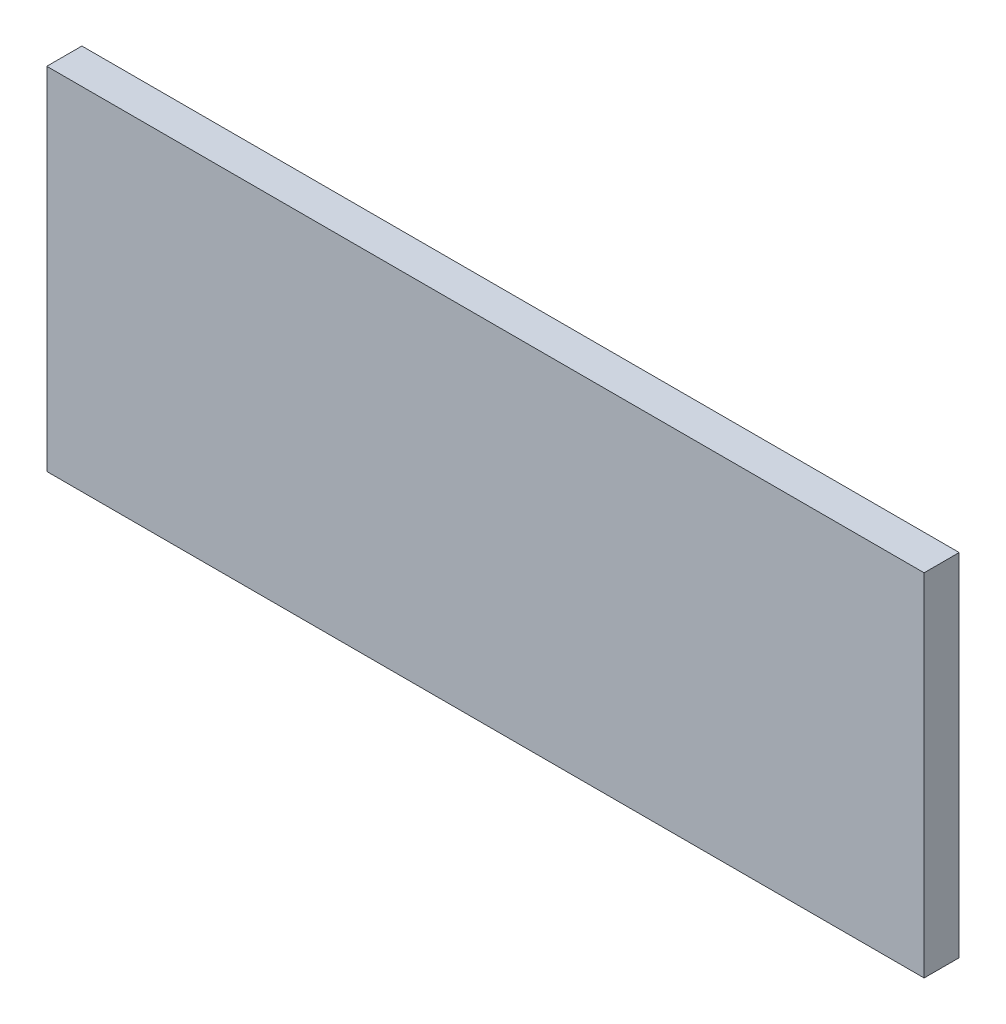
SolidWorks part; units mm, degrees
material "Лист 6,0 ГОСТ 19903-2015 / Ст3сп ГОСТ 14637-89"
ref_plane "Спереди" through (0, 0, 0) normal (0, 0, 1) x (1, 0, 0)
ref_plane "Сверху" through (0, 0, 0) normal (0, 1, 0) x (1, 0, 0)
ref_plane "Справа" through (0, 0, 0) normal (1, 0, 0) x (0, 0, -1)
sketch "Эскиз1" plane through (0, 0, 0) normal (0, 0, 1) x (1, 0, 0)
  line L1 (-75, -30) -> (75, -30)
  line L2 (-75, -30) -> (-75, 30)
  line L3 (-75, 30) -> (75, 30)
  line L4 (75, -30) -> (75, 30)
extrude "Бобышка-Вытянуть1" add sketch "Эскиз1" along normal blind 6
